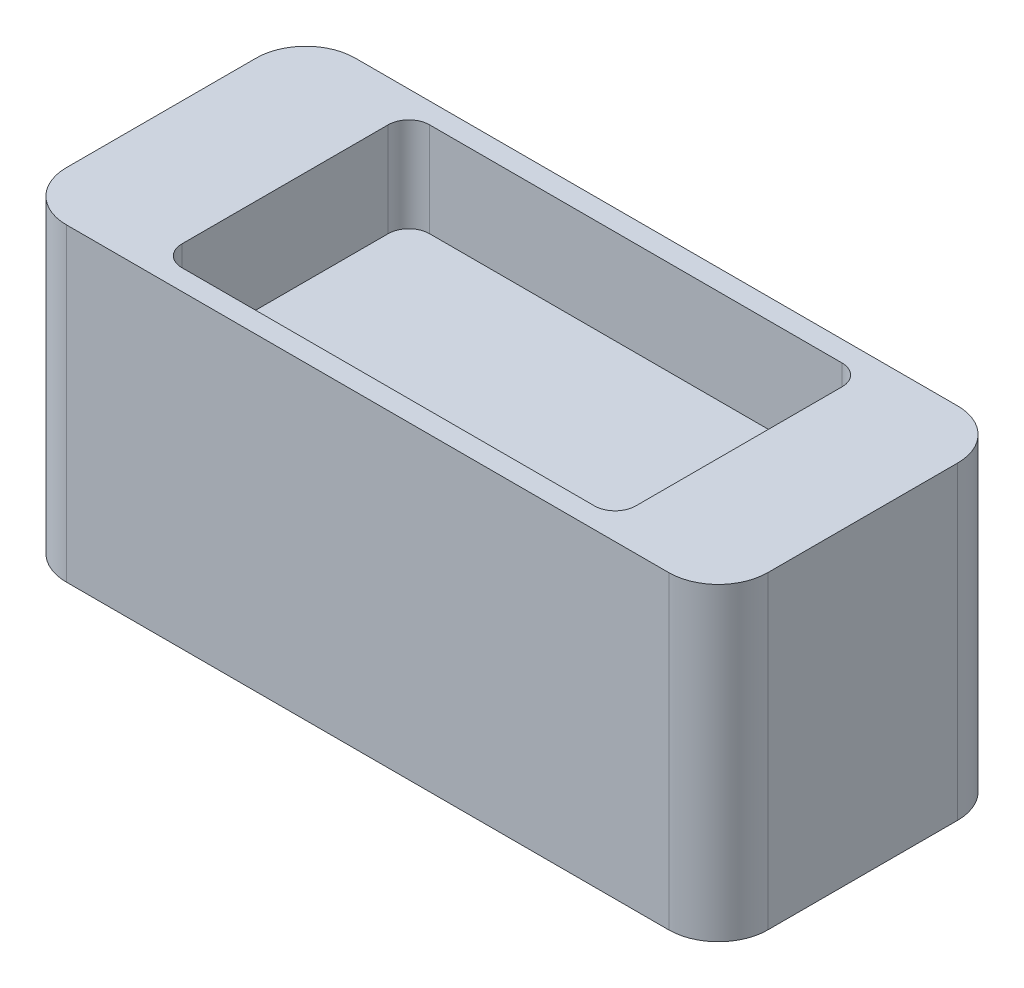
SolidWorks part; units mm, degrees
ref_plane "Front Plane" through (0, 0, 0) normal (0, 0, 1) x (1, 0, 0)
ref_plane "Top Plane" through (0, 0, 0) normal (0, 1, 0) x (1, 0, 0)
ref_plane "Right Plane" through (0, 0, 0) normal (1, 0, 0) x (0, 0, -1)
sketch "Sketch1" plane through (0, 0, 0) normal (0, 1, 0) x (1, 0, 0)
  line L6 (-730, 350) -> (730, 350)
  line L10 (-850, 230) -> (-850, -230)
  line L11 (-730, -350) -> (730, -350)
  line L12 (850, 230) -> (850, -230)
  line L13 (-850, 350) -> (850, -350) construction
  line L14 (-850, -350) -> (850, 350) construction
  line L15 (-550, 300) -> (550, 300)
  line L16 (-550, 300) -> (-550, -300)
  line L17 (-550, -300) -> (550, -300)
  line L18 (550, 300) -> (550, -300)
  line L19 (-550, 300) -> (550, -300) construction
  line L20 (-550, -300) -> (550, 300) construction
  line L21 (813, -141.1234) -> (587, -141.1234) construction
  line L22 (813, -141.1234) -> (813, 0) construction
  line L23 (813, 0) -> (587, 0) construction
  line L24 (587, -141.1234) -> (587, 0) construction
  line L25 (813, -141.1234) -> (587, 0) construction
  line L26 (813, 0) -> (587, -141.1234) construction
  arc A0 (730, -350) -> (850, -230) centre (730, -230) ccw
  arc A1 (-850, -230) -> (-730, -350) centre (-730, -230) ccw
  arc A2 (730, 350) -> (850, 230) centre (730, 230) cw
  arc A3 (-730, 350) -> (-850, 230) centre (-730, 230) ccw
  point P0 (0, 0)
  point P5 (700, -70.5617)
  point P6 (0, 0)
  dimension "D5" = 120
  dimension "D2" = 1700
  dimension "D3" = 1100
  dimension "D1" = 700
  dimension "D4" = 600
  dimension "D6" = 226
  dimension "D7" = 700
extrude "Boss-Extrude1" add sketch "Sketch1" against normal blind 750 contours L6 A3 L10 A1 L11 A0 L12 A2 L15 L18 L17 L16 | A3 L6 A2 L12 A0 L11 A1 L10 region at (0, 0, -331.6152)
extrude "Cut-Extrude1" cut sketch "Sketch1<3>" against normal blind 228.6 contours L18 L15 L16 L17 region at (0, 0, 0)
sketch "Sketch1<3>" plane through (0, 0, 0) normal (0, 1, 0) x (1, 0, 0) same geometry as "Sketch1"
fillet "Fillet1" radius 50 4 edges at (550, -114.3, 300) (-550, -114.3, 300) (550, -114.3, -300) (-550, -114.3, -300)
sketch "Sketch2" plane through (0, -750, 0) normal (0, -1, 0) x (1, 0, 0)
  line L0 (-850, -230) -> (-850, 230) construction
  line L1 (-799.2, 299.2) -> (-752.2, 299.2)
  line L2 (-799.2, 299.2) -> (-799.2, 218.7)
  line L3 (-799.2, 218.7) -> (-752.2, 218.7)
  line L4 (-752.2, 299.2) -> (-752.2, 218.7)
  line L5 (-730, 350) -> (730, 350) construction
  line L6 (0, 350) -> (0, -350) construction
  line L7 (-730, -350) -> (730, -350) construction
  line L8 (-850, 0) -> (850, 0) construction
  line L9 (850, -230) -> (850, 230) construction
  line L10 (799.2, 218.7) -> (752.2, 218.7)
  line L11 (752.2, 299.2) -> (752.2, 218.7)
  line L12 (799.2, 299.2) -> (752.2, 299.2)
  line L13 (799.2, 299.2) -> (799.2, 218.7)
  line L14 (799.2, -299.2) -> (799.2, -218.7)
  line L15 (799.2, -299.2) -> (752.2, -299.2)
  line L16 (752.2, -299.2) -> (752.2, -218.7)
  line L17 (799.2, -218.7) -> (752.2, -218.7)
  line L18 (-799.2, -218.7) -> (-752.2, -218.7)
  line L19 (-752.2, -299.2) -> (-752.2, -218.7)
  line L20 (-799.2, -299.2) -> (-752.2, -299.2)
  line L21 (-799.2, -299.2) -> (-799.2, -218.7)
  dimension "D1" = 50.8
  dimension "D2" = 50.8
  dimension "D3" = 80.5
  dimension "D4" = 47
